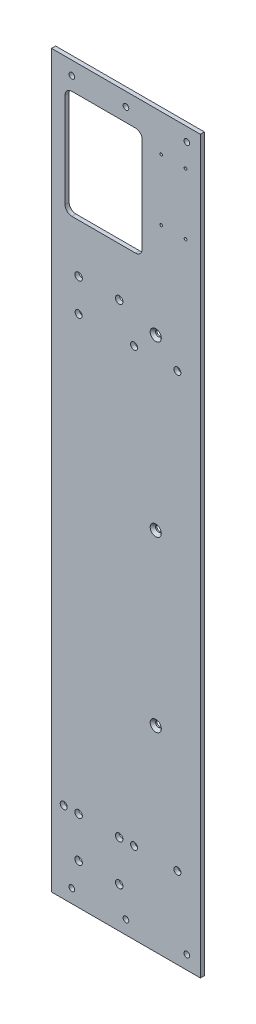
SolidWorks part; units mm, degrees
material "Thornel Mat VMA"
ref_plane "Front" through (0, 0, 0) normal (0, 0, 1) x (1, 0, 0)
ref_plane "Top" through (0, 0, 0) normal (0, 1, 0) x (1, 0, 0)
ref_plane "Right" through (0, 0, 0) normal (1, 0, 0) x (0, 0, -1)
sketch "草图1" plane through (0, 0, 0) normal (0, 0, 1) x (1, 0, 0)
  line L1 (-75, -270) -> (75, -270)
  line L2 (-75, -270) -> (-75, 270)
  line L3 (-75, 270) -> (75, 270)
  line L4 (75, -270) -> (75, 270)
  line L5 (-75, -270) -> (75, 270) construction
  line L6 (-75, 270) -> (75, -270) construction
  point P0 (0, 0)
  dimension "D1" = 150
  dimension "D2" = 540
extrude "凸台-拉伸1" add sketch "草图1" along normal blind 3
sketch "草图2" plane through (0, 0, 0) normal (0, 0, -1) x (-1, 0, 0)
  line L0 (-75, 0) -> (75, 0) construction
  line L1 (-75, -270) -> (-75, 270) construction
  line L2 (75, 270) -> (75, -270) construction
  line L3 (75, -270) -> (-75, -270) construction
  line L4 (0, -270) -> (0, -312.3628) construction
  line L5 (0, 270) -> (0, 297.7999) construction
  line L6 (-75, 270) -> (75, 270) construction
  circle A2 centre (65, -260) radius 2.1
  circle A3 centre (-65, -260) radius 2.1
  circle A6 centre (65, 260) radius 2.1
  circle A7 centre (-65, 260) radius 2.1
  circle A8 centre (-20, -260) radius 2.1
  circle A9 centre (20, -260) radius 2.1
  circle A10 centre (20, 260) radius 2.1
  circle A11 centre (-20, 260) radius 2.1
  circle A16 centre (15, 196.5) radius 1.6
  circle A17 centre (15, 188.5) radius 1.6
  circle A18 centre (-15, 196.5) radius 1.6
  circle A19 centre (-15, 188.5) radius 1.6
  dimension "D1" = 45
  dimension "D2" = 45
  dimension "D3" = 3.2
  dimension "D4" = 4.2
  dimension "D5" = 10
  dimension "D6" = 10
  dimension "D7" = 4.2
  dimension "D8" = 10
  dimension "D9" = 10
  dimension "D10" = 30
  dimension "D11" = 8
  dimension "D12" = 73.5
extrude "切除-拉伸1" cut sketch "草图2" against normal through all
sketch "草图3" plane through (0, 0, 3) normal (0, 0, 1) x (1, 0, 0)
  line L1 (75, -270) -> (75, 270) construction
  circle A0 centre (65, 30) radius 1.5
  circle A1 centre (65, -30) radius 1.5
  dimension "D1" = 3
  dimension "D2" = 10
  dimension "D3" = 30
  dimension "D4" = 3
  dimension "D5" = 30
  dimension "D6" = 10
sketch "草图4" plane through (0, 0, 3) normal (0, 0, 1) x (1, 0, 0)
  line L0 (42, 0) -> (140.7159, 0) construction
  line L1 (75, -270) -> (75, 270) construction
  line L2 (0, 270) -> (0, -270) construction
  line L3 (75, 270) -> (-75, 270) construction
  line L4 (-75, -270) -> (75, -270) construction
  line L5 (-42, 0) -> (-140.7159, 0) construction
  circle A0 centre (42, 125) radius 2.1
  circle A1 centre (42, -125) radius 2.1
  circle A2 centre (42, 0) radius 2.1
  circle A3 centre (-42, 0) radius 2.1
  circle A4 centre (-42, -125) radius 2.1
  circle A5 centre (-42, 125) radius 2.1
  dimension "D1" = 250
  dimension "D2" = 4.2
  dimension "D3" = 4.2
  dimension "D4" = 33
  dimension "D5" = 33
extrude "切除-拉伸2" cut sketch "草图4" against normal up to next
chamfer "倒角1" distance 2 angle 45 3 edges at (44.1, 0, 3) (39.9, -125, 3) (44.1, 125, 3)
sketch "草图6" plane through (0, 0, 3) normal (0, 0, 1) x (1, 0, 0)
  line L0 (0, -286.6484) -> (0, 69.1326) construction
  line L1 (-75, -270) -> (75, -270) construction
  line L2 (-75, 270) -> (-75, -270) construction
  line L3 (75, -270) -> (75, 270) construction
  line L6 (75, 270) -> (-75, 270) construction
  circle A1 centre (26, -210) radius 2.6
  circle A4 centre (-26, -210) radius 2.6
  circle A5 centre (58, -210) radius 2.6
  circle A6 centre (-58, -210) radius 2.6
  circle A9 centre (-47, 110) radius 2.6
  circle A10 centre (-15, 110) radius 2.6
  circle A11 centre (26, 110) radius 2.6
  circle A12 centre (58, 110) radius 2.6
  dimension "D1" = 5.2
  dimension "D2" = 17
  dimension "D3" = 60
  dimension "D4" = 32
  dimension "D5" = 5.2
  dimension "D6" = 5.2
  dimension "D7" = 5.2
  dimension "D8" = 5.2
  dimension "D9" = 32
  dimension "D10" = 17
  dimension "D11" = 32
  dimension "D12" = 28
  dimension "D14" = 160
  dimension "D15" = 160
  dimension "D16" = 160
extrude "切除-拉伸4" cut sketch "草图6" against normal up to next
sketch "草图7" plane through (0, 0, 3) normal (0, 0, 1) x (1, 0, 0)
  line L4 (75, -270) -> (75, 270)
  line L5 (75, 270) -> (-75, 270)
  line L6 (-75, 270) -> (-75, -270)
  line L7 (-75, -270) -> (75, -270)
  line L8 (75, -270) -> (75, 270)
  line L9 (75, 270) -> (-75, 270)
  line L10 (-75, 270) -> (-75, -270)
  line L11 (-75, -270) -> (75, -270)
  circle A2 centre (-15, 134) radius 2.75
  circle A3 centre (15, 134) radius 2.75
  dimension "D2" = 136
  dimension "D3" = 5.5
  dimension "D5" = 30
  dimension "D6" = 5.5
  dimension "D7" = 60
  dimension "D4" = 136
  dimension "D1" = 0
extrude "切除-拉伸5" cut sketch "草图7" against normal up to next contours A2 | A3 region at (-15, 134, 3)
sketch "草图8" plane through (0, 0, 3) normal (0, 0, 1) x (1, 0, 0)
  line L4 (75, -270) -> (75, 270)
  line L5 (75, 270) -> (-75, 270)
  line L6 (-75, 270) -> (-75, -270)
  line L7 (-75, -270) -> (75, -270)
  line L8 (75, -270) -> (75, 270)
  line L9 (75, 270) -> (-75, 270)
  line L10 (-75, 270) -> (-75, -270)
  line L11 (-75, -270) -> (75, -270)
  circle A2 centre (-15, -210) radius 2.75
  circle A3 centre (15, -210) radius 2.75
  dimension "D2" = 5.5
  dimension "D3" = 5.5
  dimension "D4" = 30
  dimension "D5" = 60
  dimension "D6" = 60
  dimension "D7" = 60
  dimension "D1" = 0
extrude "切除-拉伸6" cut sketch "草图8" against normal up to next contours A2 | A3 region at (-15, -210, 3) region at (15, -210, 3)
sketch "草图9" plane through (0, 0, 3) normal (0, 0, 1) x (1, 0, 0)
  line L0 (0, -270) -> (0, -79.9483) construction
  line L1 (-75, -270) -> (75, -270) construction
  circle A0 centre (-15, -240) radius 2.75
  circle A1 centre (15, -240) radius 2.75
  dimension "D1" = 5.5
  dimension "D2" = 30
  dimension "D3" = 30
extrude "切除-拉伸7" cut sketch "草图9" against normal blind 10
sketch "草图10" plane through (0, 0, 3) normal (0, 0, 1) x (1, 0, 0)
  line L0 (0, 270) -> (0, 151.6479) construction
  line L1 (75, 270) -> (-75, 270) construction
  line L2 (-25, 170) -> (-25, 250)
  line L3 (-25, 170) -> (25, 170)
  line L4 (0, 170) -> (0, 250)
  line L5 (-25, 250) -> (25, 250)
  line L6 (25, 170) -> (25, 250)
  line L8 (25, 250) -> (32, 250)
  line L9 (25, 250) -> (25, 170)
  line L10 (25, 170) -> (32, 170)
  line L11 (32, 250) -> (32, 170)
  circle M23 centre (-15, 196.5) radius 1.6
  circle M28 centre (15, 188.5) radius 1.6
  circle M29 centre (15, 196.5) radius 1.6
  circle M30 centre (-15, 188.5) radius 1.6
  dimension "D1" = 50
  dimension "D2" = 20
  dimension "D3" = 80
  dimension "D4" = 7
extrude "切除-拉伸8" cut sketch "草图10" against normal blind 10 contours L5 L2 L3 L4 M30 M23 | L3 L6 L5 L4 M28 M29 | L11 L8 L6 L10 region at (-12.4797, 210.1419, 3) region at (12.4797, 210.1419, 3) region at (28.5, 210, 3)
fillet "圆角1" radius 5 4 edges at (-25, 170, 1.5) (-25, 250, 1.5) (32, 170, 1.5) (32, 250, 1.5)
sketch "草图11" plane through (0, 0, 3) normal (0, 0, 1) x (1, 0, 0)
  line L0 (55, 266.5246) -> (55, 192.9358) construction
  line L1 (-66.7226, 220) -> (-27.8973, 220) construction
  line L2 (-75, 270) -> (-75, -270) construction
  line L3 (75, 270) -> (-75, 270) construction
  circle A0 centre (46, 242.6) radius 1
  circle A1 centre (64, 242.6) radius 1
  circle A2 centre (64, 197.4) radius 1
  circle A3 centre (46, 197.4) radius 1
  dimension "D1" = 2
  dimension "D2" = 18
  dimension "D3" = 45.2
  dimension "D4" = 130
  dimension "D5" = 50
extrude "切除-拉伸9" cut sketch "草图11" against normal blind 4
sketch "草图13" plane through (0, 0, 3) normal (0, 0, 1) x (1, 0, 0)
  line L0 (-35, 270) -> (-35, -270)
  line L1 (75, 270) -> (-75, 270) construction
  line L2 (-75, -270) -> (75, -270) construction
  line L4 (-35, 270) -> (-236.483, 270)
  line L5 (-35, 270) -> (-35, -387.7593)
  line L6 (-35, -387.7593) -> (-236.483, -387.7593)
  line L7 (-236.483, 270) -> (-236.483, -387.7593)
  circle A0 centre (-20, 260) radius 2.1 construction
  line M10 (75, 270) -> (-75, 270)
  line M11 (-75, 270) -> (-75, -270)
  line M12 (-75, -270) -> (75, -270)
  circle M16 centre (-65, -260) radius 2.1
  circle M20 centre (-65, 260) radius 2.1
  circle M27 centre (-47, 110) radius 2.6
  circle M28 centre (-58, -210) radius 2.6
  dimension "D1" = 15
extrude "切除-拉伸10" cut sketch "草图13" against normal blind 10 contours L0 M10 M11 M12 M16 M20 M28 M27 region at (-54.9921, 0.0986, 3)
